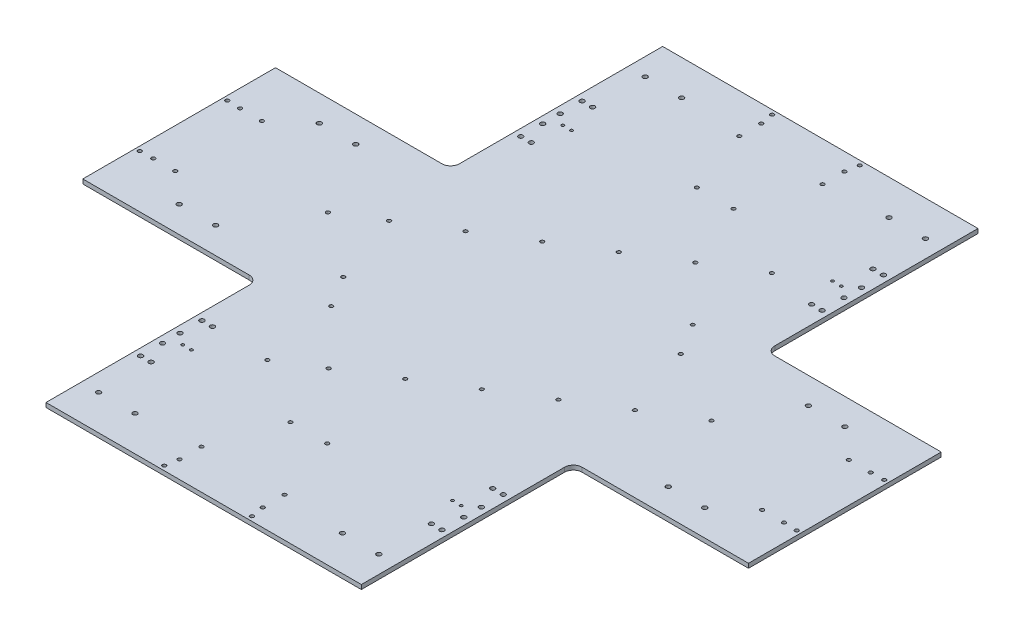
SolidWorks part; units mm, degrees
other "Markup1"
sketch "Sketch8"
material "3.0205 (EN-AW 1200)"
ref_plane "前视基准面" through (0, 0, 0) normal (0, 0, 1) x (1, 0, 0)
ref_plane "上视基准面" through (0, 0, 0) normal (0, 1, 0) x (1, 0, 0)
ref_plane "右视基准面" through (0, 0, 0) normal (1, 0, 0) x (0, 0, -1)
other "Configuration Table"
sketch "Sketch1" plane through (0, 0, 0) normal (0, 1, 0) x (1, 0, 0)
  line L0 (180, 352) -> (-180, 352)
  line L1 (-180, 352) -> (-180, 110)
  line L2 (-180, 110) -> (-380, 110)
  line L5 (-380, 110) -> (-380, -110)
  line L6 (0, 352) -> (0, -66.8675) construction
  line L7 (-380, 0) -> (131.0517, 0) construction
  line L8 (380, 110) -> (380, -110)
  line L11 (180, 110) -> (380, 110)
  line L12 (180, 352) -> (180, 110)
  line L13 (180, -352) -> (180, -110)
  line L14 (180, -110) -> (380, -110)
  line L19 (-180, -110) -> (-380, -110)
  line L20 (-180, -352) -> (-180, -110)
  line L21 (180, -352) -> (-180, -352)
  point P21 (380, 0)
  dimension "D1" = 180
  dimension "D2" = 200
  dimension "D3" = 110
  dimension "D4" = 242
extrude "Boss-Extrude1" add sketch "Sketch1" along normal blind 5
sketch "Sketch2" plane through (0, 5, 0) normal (0, 1, 0) x (1, 0, 0)
  line L3 (380, -110) -> (380, 110) construction
  line L4 (-56.7455, 0) -> (47.5165, 0) construction
  line L5 (0, 54.7142) -> (0, -64.2255) construction
  line L7 (180, 352) -> (-180, 352) construction
  circle A0 centre (360, 49.5) radius 2.125
  circle A1 centre (335, 49.5) radius 2.125
  circle A7 centre (335, -49.5) radius 2.125
  circle A8 centre (360, -49.5) radius 2.125
  circle A9 centre (-360, -49.5) radius 2.125
  circle A10 centre (-335, -49.5) radius 2.125
  circle A13 centre (-335, 49.5) radius 2.125
  circle A14 centre (-360, 49.5) radius 2.125
  circle A15 centre (47.5, 332) radius 2.125
  circle A16 centre (47.5, 307) radius 2.125
  circle A17 centre (-47.5, 307) radius 2.125
  circle A18 centre (-47.5, 332) radius 2.125
  circle A19 centre (-47.5, -332) radius 2.125
  circle A20 centre (-47.5, -307) radius 2.125
  circle A21 centre (47.5, -307) radius 2.125
  circle A22 centre (47.5, -332) radius 2.125
  dimension "D3" = 49.5
  dimension "D5" = 4.25
  dimension "D7" = 4.25
  dimension "D9" = 4.25
  dimension "D10" = 4.25
  dimension "D2" = 47.5
  dimension "D4" = 25
  dimension "D6" = 20
  dimension "20" = 20
  dimension "D13" = 25
extrude "Cut-Extrude1" cut sketch "Sketch2" against normal blind 3
sketch "Sketch4" plane through (0, 5, 0) normal (0, 1, 0) x (1, 0, 0)
  line L0 (-180, 352) -> (-180, 110) construction
  line L1 (180, 352) -> (-180, 352) construction
  line L2 (0, 46.9886) -> (0, -40.2904) construction
  line L3 (-35.103, 0) -> (92.4951, 0) construction
  line L5 (180, -352) -> (180, -110) construction
  circle A0 centre (-172, 182) radius 2.6
  circle A1 centre (-160, 182) radius 2.6
  circle A2 centre (-172, 207) radius 2.6
  circle A3 centre (-172, 227) radius 2.6
  circle A4 centre (-172, 252) radius 2.6
  circle A5 centre (-160, 252) radius 2.6
  circle A6 centre (160, 252) radius 2.6
  circle A7 centre (172, 252) radius 2.6
  circle A8 centre (172, 227) radius 2.6
  circle A9 centre (172, 207) radius 2.6
  circle A10 centre (160, 182) radius 2.6
  circle A11 centre (172, 182) radius 2.6
  circle A12 centre (172, -182) radius 2.6
  circle A13 centre (160, -182) radius 2.6
  circle A14 centre (172, -207) radius 2.6
  circle A15 centre (172, -227) radius 2.6
  circle A16 centre (172, -252) radius 2.6
  circle A17 centre (160, -252) radius 2.6
  circle A18 centre (-160, -252) radius 2.6
  circle A19 centre (-172, -252) radius 2.6
  circle A20 centre (-172, -227) radius 2.6
  circle A21 centre (-172, -207) radius 2.6
  circle A22 centre (-160, -182) radius 2.6
  circle A23 centre (-172, -182) radius 2.6
  circle A24 centre (159, -217) radius 1.6
  circle A25 centre (-159, -217) radius 1.6
  circle A26 centre (159, 217) radius 1.6
  circle A27 centre (-159, 217) radius 1.6
  circle A28 centre (149, -217) radius 1.6
  circle A29 centre (-149, -217) radius 1.6
  circle A30 centre (149, 217) radius 1.6
  circle A31 centre (-149, 217) radius 1.6
  dimension "D3" = 5.2
  dimension "D4" = 5.2
  dimension "D5" = 8
  dimension "D6" = 8
  dimension "D9" = 5.2
  dimension "D10" = 5.2
  dimension "D11" = 5.2
  dimension "D12" = 5.2
  dimension "D19" = 3.2
  dimension "D20" = 21
  dimension "D21" = 10
  dimension "D22" = 3.2
  dimension "D23" = 10
  dimension "D1" = 8
  dimension "D2" = 20
  dimension "D7" = 8
  dimension "D8" = 20
  dimension "D13" = 25
  dimension "D14" = 20
  dimension "D15" = 25
  dimension "D16" = 25
  dimension "D17" = 100
  dimension "D18" = 0
extrude "Cut-Extrude3" cut sketch "Sketch4" against normal blind 10
sketch "Sketch5" plane through (0, 5, 0) normal (0, 1, 0) x (1, 0, 0)
  line L0 (180, 352) -> (-180, 352) construction
  line L5 (-46.9195, 0) -> (66.6223, 0) construction
  line L6 (0, 59.0569) -> (0, -54.4849) construction
  line L10 (-380, 110) -> (-380, -110) construction
  circle A0 centre (-50, 347) radius 2.125
  circle A1 centre (50, 347) radius 2.125
  circle A2 centre (50, -347) radius 2.125
  circle A3 centre (-50, -347) radius 2.125
  circle A4 centre (-375, 50) radius 2.125
  circle A5 centre (-375, -50) radius 2.125
  circle A6 centre (375, -50) radius 2.125
  circle A7 centre (375, 50) radius 2.125
  dimension "D1" = 4.25
  dimension "D2" = 4.25
  dimension "D3" = 50
  dimension "D6" = 4.25
  dimension "D7" = 4.25
  dimension "5" = 5
  dimension "D4" = 50
  dimension "D5" = 50
  dimension "D8" = 50
  dimension "D9" = 5
  dimension "D10" = 5
extrude "Cut-Extrude4" cut sketch "Sketch5" against normal blind 10
fillet "Fillet1" radius 10 4 edges at (-180, 2.5, -110) (-180, 2.5, 110) (180, 2.5, 110) (180, 2.5, -110)
sketch "Sketch6" plane through (0, 5, 0) normal (0, 1, 0) x (1, 0, 0)
  line L0 (180, 352) -> (-180, 352) construction
  line L1 (-180, 352) -> (-180, 120) construction
  line L3 (0, 50.3702) -> (0, -42.7646) construction
  line L4 (-54.8568, 0) -> (91.2004, 0) construction
  line L5 (380, 110) -> (190, 110) construction
  line L6 (380, -110) -> (380, 110) construction
  circle A0 centre (-160, 312) radius 2.6
  circle A1 centre (-118.4, 312) radius 2.6
  circle A4 centre (118.4, 312) radius 2.6
  circle A5 centre (160, 312) radius 2.6
  circle A6 centre (160, -312) radius 2.6
  circle A7 centre (118.4, -312) radius 2.6
  circle A8 centre (-118.4, -312) radius 2.6
  circle A9 centre (-160, -312) radius 2.6
  circle A10 centre (258.4, 80) radius 2.6
  circle A11 centre (300, 80) radius 2.6
  circle A12 centre (300, -80) radius 2.6
  circle A13 centre (258.4, -80) radius 2.6
  circle A14 centre (-258.4, -80) radius 2.6
  circle A15 centre (-300, -80) radius 2.6
  circle A16 centre (-300, 80) radius 2.6
  circle A17 centre (-258.4, 80) radius 2.6
  dimension "D1" = 5.2
  dimension "D2" = 5.2
  dimension "D3" = 5.2
  dimension "D4" = 5.2
  dimension "D5" = 40
  dimension "D8" = 30
  dimension "D6" = 20
  dimension "D7" = 41.6
  dimension "D9" = 80
  dimension "D10" = 41.6
extrude "Cut-Extrude5" cut sketch "Sketch6" against normal blind 10
sketch "Sketch7" plane through (0, 5, 0) normal (0, 1, 0) x (1, 0, 0)
  line L0 (182.9289, 112.9289) -> (-182.9289, -112.9289) construction
  line L1 (180, 235.6925) -> (-379.973, -110) construction
  line L2 (180, 120) -> (180, 352) construction
  line L3 (-380, -110) -> (-190, -110) construction
  line L4 (379.973, 110) -> (-180, -235.6925) construction
  line L5 (380, 110) -> (190, 110) construction
  line L6 (-180, -120) -> (-180, -352) construction
  line L7 (-252.1038, -38.9487) -> (-83.0161, -312.847) construction
  line L8 (99.6992, 266.786) -> (288.8891, -39.6749) construction
  line L9 (-55.682, 90.1971) -> (55.682, -90.1971) construction
  arc A0 (180, 120) -> (190, 110) centre (190, 120) ccw construction
  arc A1 (-180, -120) -> (-190, -110) centre (-190, -120) ccw construction
  circle A4 centre (-55.682, 90.1971) radius 2.125
  circle A5 centre (-1.6489, 123.5538) radius 2.125
  circle A6 centre (52.3842, 156.9105) radius 2.125
  circle A7 centre (106.4174, 190.2672) radius 2.125
  circle A8 centre (-109.7152, 56.8404) radius 2.125
  circle A9 centre (-163.7483, 23.4837) radius 2.125
  circle A10 centre (-206.9749, -3.2017) radius 2.125
  circle A11 centre (-95.6108, -183.5958) radius 2.125
  circle A12 centre (-52.3842, -156.9105) radius 2.125
  circle A13 centre (1.6489, -123.5538) radius 2.125
  circle A14 centre (217.7815, 9.873) radius 2.125
  circle A15 centre (163.7483, -23.4837) radius 2.125
  circle A16 centre (109.7152, -56.8404) radius 2.125
  circle A17 centre (55.682, -90.1971) radius 2.125
  dimension "D6" = 4.25
  dimension "D7" = 4.25
  dimension "D8" = 4.25
  dimension "D9" = 4.25
  dimension "D10" = 4.25
  dimension "D11" = 4.25
  dimension "D12" = 4.25
  dimension "D1" = 106
  dimension "D3" = 20
  dimension "D4" = 20
  dimension "D5" = 0
  dimension "D13" = 63.5
  dimension "D14" = 63.5
  dimension "D15" = 50.8
  dimension "D16" = 63.5
  dimension "D17" = 63.5
  dimension "D18" = 63.5
extrude "Cut-Extrude6" cut sketch "Sketch7" against normal blind 10
sketch "Sketch9" plane through (0, 5, 0) normal (0, 1, 0) x (1, 0, 0)
  line L0 (182.9289, 112.9289) -> (-182.9289, -112.9289) construction
  line L1 (92.6836, 125.8571) -> (158.1979, 19.7331) construction
  line L2 (-151.014, -31.37) -> (-99.0832, -115.4905) construction
  line L3 (0, 45.0584) -> (0, -52.9183) construction
  line L4 (-44.6513, 0) -> (48.0404, 0) construction
  line L5 (180, 352) -> (-180, 352) construction
  arc A0 (180, 120) -> (190, 110) centre (190, 120) ccw construction
  arc A1 (-180, -120) -> (-190, -110) centre (-190, -120) ccw construction
  circle A2 centre (-134.3962, -58.2885) radius 2.1
  circle A3 centre (-112.3335, -94.027) radius 2.1
  circle A4 centre (112.3335, 94.027) radius 2.1
  circle A5 centre (134.3962, 58.2885) radius 2.1
  circle A7 centre (21, 232) radius 2.1
  circle A8 centre (-21, 232) radius 2.1
  circle A9 centre (-21, -232) radius 2.1
  circle A10 centre (21, -232) radius 2.1
  dimension "D3" = 4.2
  dimension "D4" = 4.2
  dimension "D5" = 4.2
  dimension "D6" = 4.2
  dimension "D11" = 120
  dimension "D12" = 4.2
  dimension "D1" = 70
  dimension "D2" = 70
  dimension "D7" = 21
  dimension "D8" = 21
  dimension "D9" = 21
  dimension "D10" = 21
  dimension "D13" = 21
extrude "Cut-Extrude7" cut sketch "Sketch9" against normal blind 10
